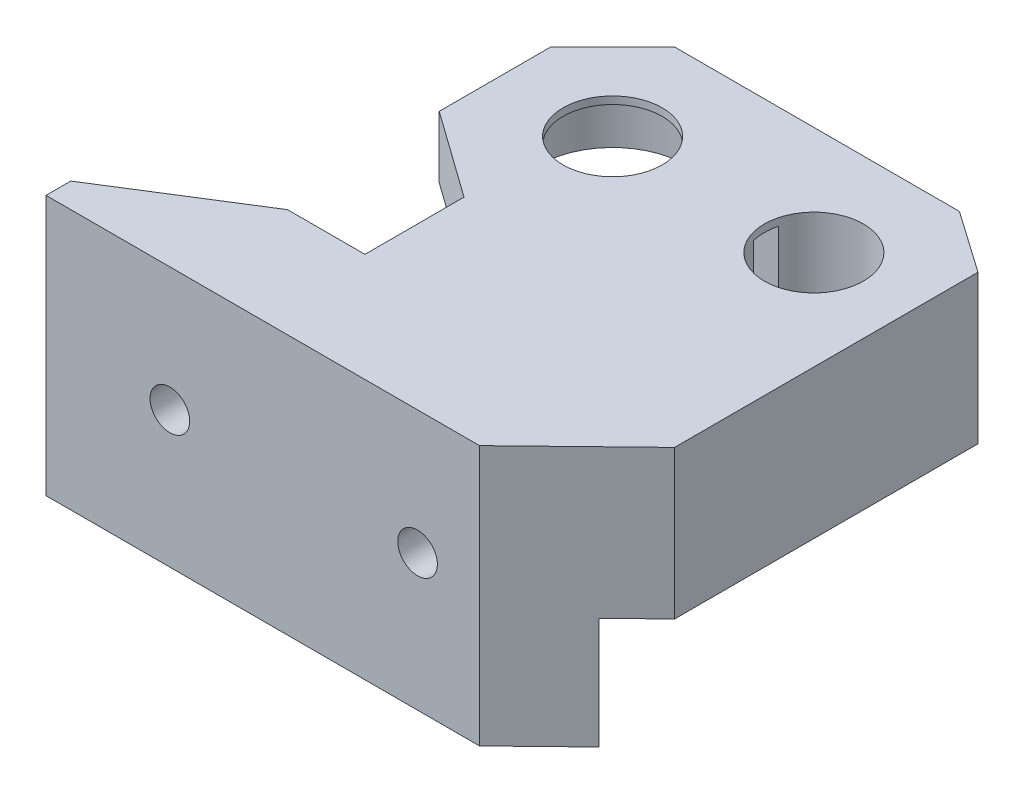
SolidWorks part; units mm, degrees
ref_plane "Front Plane" through (0, 0, 0) normal (0, 0, 1) x (1, 0, 0)
ref_plane "Top Plane" through (0, 0, 0) normal (0, 1, 0) x (1, 0, 0)
ref_plane "Right Plane" through (0, 0, 0) normal (1, 0, 0) x (0, 0, -1)
sketch "Sketch1" plane through (0, 0, 0) normal (0, 1, 0) x (1, 0, 0)
  line L0 (0, 0) -> (16.25, 0) construction
  line L5 (-3.75, 8.75) -> (19.25, 8.75)
  line L6 (19.25, 8.75) -> (24.25, 5.25)
  line L7 (24.25, 5.25) -> (24.25, -19.25)
  line L8 (24.25, -19.25) -> (16.25, -27)
  line L9 (16.25, -27) -> (-18.75, -27)
  line L10 (-18.75, -27) -> (-18.75, -25)
  line L11 (-18.75, -25) -> (-8, -18.25)
  line L12 (-8, -18.25) -> (-1.75, -18.25)
  line L13 (-1.75, -18.25) -> (-1.75, -10.25)
  line L14 (-1.75, -10.25) -> (-8.75, -5.25)
  line L15 (-8.75, -5.25) -> (-8.75, 3.75)
  line L16 (-8.75, 3.75) -> (-3.75, 8.75)
  line L17 (16.25, 0) -> (24.25, 0) construction
  circle A0 centre (0, 0) radius 4
  circle A1 centre (16.25, 0) radius 4
  point P0 (0, 0)
  dimension "D2" = 8
  dimension "D3" = 8
  dimension "D1" = 16.25
  dimension "D4" = 23
  dimension "D5" = 5
  dimension "D6" = 3.5
  dimension "D7" = 24.5
  dimension "D8" = 8
  dimension "D9" = 8.75
  dimension "D10" = 5
  dimension "D11" = 5
  dimension "D12" = 7
  dimension "D13" = 5
  dimension "D14" = 9
  dimension "D15" = 8
  dimension "D16" = 7.75
  dimension "D17" = 35
  dimension "D18" = 6.25
  dimension "D19" = 6.75
  dimension "D20" = 2
extrude "Boss-Extrude1" add sketch "Sketch1" along normal blind 5
sketch "Sketch2" plane through (0, 0, 0) normal (0, -1, 0) x (1, 0, 0)
  line L0 (24.25, 19.25) -> (24.25, -5.25)
  line L1 (24.25, -5.25) -> (20.75, -5.25)
  line L2 (20.75, -5.25) -> (20.75, 18.25)
  line L3 (20.75, 18.25) -> (-8, 18.25)
  line L4 (-8, 18.25) -> (-14.3704, 22.25)
  line L5 (-8, 18.25) -> (-18.75, 25) construction
  line L6 (-14.3704, 22.25) -> (21.1532, 22.25)
  line L7 (16.25, 27) -> (24.25, 19.25) construction
  line L8 (21.1532, 22.25) -> (24.25, 19.25)
  dimension "D1" = 3.5
  dimension "D2" = 4
extrude "Boss-Extrude2" add sketch "Sketch2" along normal blind 7
sketch "Sketch3" plane through (0, 0, 0) normal (0, -1, 0) x (1, 0, 0)
  line L5 (-14.3704, 22.25) -> (21.1532, 22.25)
  line L6 (21.1532, 22.25) -> (16.25, 27)
  line L7 (16.25, 27) -> (-18.75, 27)
  line L8 (-18.75, 27) -> (-18.75, 25)
  line L9 (-18.75, 25) -> (-14.3704, 22.25)
  line L10 (-14.3704, 22.25) -> (21.1532, 22.25)
  line L11 (21.1532, 22.25) -> (16.25, 27)
  line L12 (16.25, 27) -> (-18.75, 27)
  line L13 (-18.75, 27) -> (-18.75, 25)
  line L14 (-18.75, 25) -> (-14.3704, 22.25)
  dimension "D1" = 0
extrude "Boss-Extrude3" add sketch "Sketch3" along normal blind 16
sketch "Sketch6" plane through (0, 0, 0) normal (0, -1, 0) x (1, 0, 0)
  circle A0 centre (16.25, 0) radius 7
  circle A1 centre (16.25, 0) radius 4
  dimension "D1" = 14
extrude "Boss-Extrude4" add sketch "Sketch6" along normal blind 2.5
sketch "Sketch4" plane through (0, 0, 0) normal (0, -1, 0) x (1, 0, 0)
  line L0 (0, 0) -> (12.25, 0) construction
  line L1 (5.8838, -1) -> (12.377, -1)
  line L2 (5.8838, 1) -> (12.377, 1)
  line L3 (0, -1) -> (16.25, -1) construction
  line L4 (0, 1) -> (16.25, 1) construction
  line L5 (0, 0) -> (16.25, 0) construction
  arc A0 (5.8838, 1) -> (5.8838, -1) centre (0, 0) ccw
  arc A2 (12.377, 1) -> (12.377, -1) centre (16.25, 0) ccw
  dimension "D1" = 1
  dimension "D2" = 1
extrude "Cut-Extrude1" cut sketch "Sketch4" against normal blind 4.4
sketch "Sketch7" plane through (0, 4.4, 0) normal (0, -1, 0) x (1, 0, 0)
  line L2 (5.8838, -1) -> (12.377, -1)
  line L3 (12.377, 1) -> (5.8838, 1)
  line L4 (5.8838, -1) -> (12.377, -1)
  line L5 (12.377, 1) -> (5.8838, 1)
  arc A2 (5.8838, 1) -> (5.8838, -1) centre (0, 0) ccw
  arc A3 (12.377, 1) -> (12.377, -1) centre (16.25, 0) ccw
  arc A4 (5.8838, 1) -> (5.8838, -1) centre (0, 0) ccw
  arc A5 (12.377, 1) -> (12.377, -1) centre (16.25, 0) ccw
  dimension "D1" = 0
extrude "Cut-Extrude2" cut sketch "Sketch7" along normal through all
sketch "Sketch8" plane through (0, 0, 27) normal (0, 0, 1) x (1, 0, 0)
  line L0 (11.25, -5) -> (-8.75, -5) construction
  line L1 (-18.75, 5) -> (16.25, 5) construction
  line L2 (-18.75, 5) -> (-18.75, -16) construction
  circle A0 centre (11.25, -5) radius 1.6
  circle A1 centre (-8.75, -5) radius 1.6
  dimension "D1" = 3.2
  dimension "D2" = 3.2
  dimension "D3" = 20
  dimension "D4" = 10
  dimension "D5" = 10
extrude "Cut-Extrude3" cut sketch "Sketch8" against normal through all
sketch "Sketch9" plane through (0, 0, 18.25) normal (0, 0, -1) x (-1, 0, 0)
  circle A0 centre (-11.25, -5) radius 3
  circle A1 centre (8.75, -5) radius 3
  dimension "D1" = 6
  dimension "D2" = 6
extrude "Cut-Extrude4" cut sketch "Sketch9" against normal blind 4
